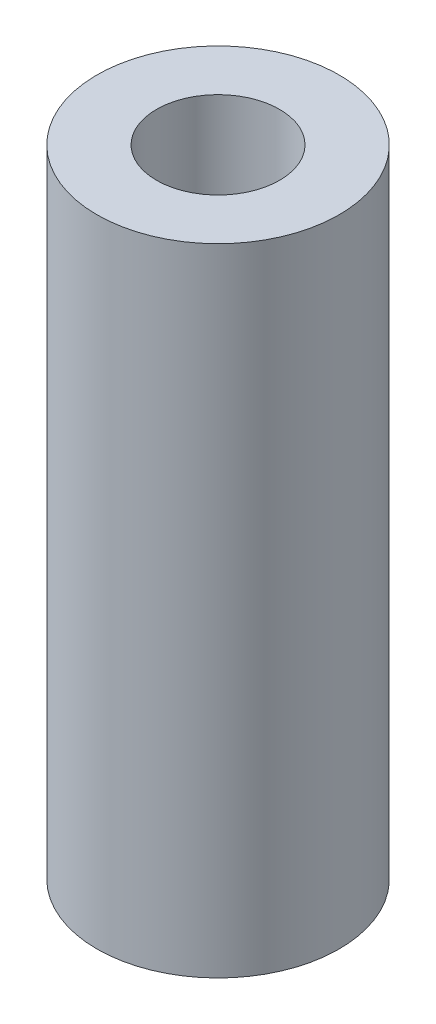
SolidWorks part; units mm, degrees
ref_plane "Front Plane" through (0, 0, 0) normal (0, 0, 1) x (1, 0, 0)
ref_plane "Top Plane" through (0, 0, 0) normal (0, 1, 0) x (1, 0, 0)
ref_plane "Right Plane" through (0, 0, 0) normal (1, 0, 0) x (0, 0, -1)
sketch "Sketch1" plane through (0, 0, 0) normal (0, 1, 0) x (1, 0, 0)
  circle A0 centre (0, 0) radius 6.35
  arc A4 (5.8475, -2.4757) -> (-4.4116, 4.5673) centre (0, 0) ccw construction
  circle A5 centre (0, 0) radius 3.2258
  circle A6 centre (0, 0) radius 3.2258
  dimension "D1" = 0.0508
extrude "Boss-Extrude1" add sketch "Sketch1" along normal up to surface (33.3375 mm away)
